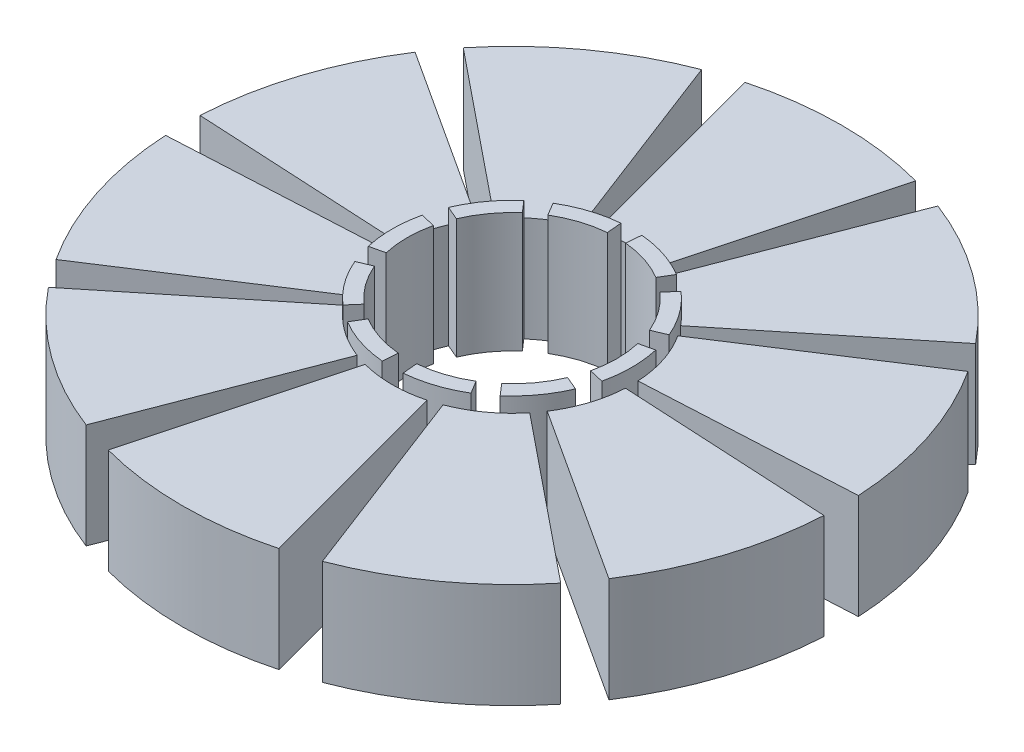
SolidWorks part; units mm, degrees
material "Copper"
ref_plane "Front Plane" through (0, 0, 0) normal (0, 0, 1) x (1, 0, 0)
ref_plane "Top Plane" through (0, 0, 0) normal (0, 1, 0) x (1, 0, 0)
ref_plane "Right Plane" through (0, 0, 0) normal (1, 0, 0) x (0, 0, -1)
sketch "Sketch2" plane through (0, 0, 0) normal (0, 1, 0) x (1, 0, 0)
  line L0 (0, 0) -> (0, 8) construction
  line L1 (0, 0) -> (1.8117, 6.7615) construction
  line L2 (0, 0) -> (-1.8117, 6.7615) construction
  line L3 (-5.694, 21.2504) -> (-2.0706, 7.7274)
  line L4 (2.0706, 7.7274) -> (5.694, 21.2504)
  line L5 (0, 0) -> (4.7023, 6.4721) construction
  line L6 (7.8841, 20.5388) -> (2.8669, 7.4686)
  line L7 (6.2172, 5.0346) -> (17.0972, 13.845)
  line L8 (0, 0) -> (7.6085, 2.4721) construction
  line L9 (18.4508, 11.9821) -> (6.7094, 4.3571)
  line L10 (7.989, 0.4187) -> (21.9698, 1.1514)
  line L11 (0, 0) -> (19.9722, -6.4894) construction
  line L12 (21.9698, -1.1514) -> (7.989, -0.4187)
  line L13 (6.7094, -4.3571) -> (18.4508, -11.9821)
  line L14 (0, 0) -> (4.7023, -6.4721) construction
  line L15 (17.0972, -13.845) -> (6.2172, -5.0346)
  line L16 (2.8669, -7.4686) -> (7.8841, -20.5388)
  line L17 (0, 0) -> (0, -8) construction
  line L18 (5.694, -21.2504) -> (2.0706, -7.7274)
  line L19 (-2.0706, -7.7274) -> (-5.694, -21.2504)
  line L20 (0, 0) -> (-4.7023, -6.4721) construction
  line L21 (-7.8841, -20.5388) -> (-2.8669, -7.4686)
  line L22 (-6.2172, -5.0346) -> (-17.0972, -13.845)
  line L23 (0, 0) -> (-7.6085, -2.4721) construction
  line L24 (-18.4508, -11.9821) -> (-6.7094, -4.3571)
  line L25 (-7.989, -0.4187) -> (-21.9698, -1.1514)
  line L26 (0, 0) -> (-7.6085, 2.4721) construction
  line L27 (-21.9698, 1.1514) -> (-7.989, 0.4187)
  line L28 (-6.7094, 4.3571) -> (-18.4508, 11.9821)
  line L29 (0, 0) -> (-4.7023, 6.4721) construction
  line L30 (-17.0972, 13.845) -> (-6.2172, 5.0346)
  line L31 (-2.8669, 7.4686) -> (-7.8841, 20.5388)
  line L32 (0.6101, 6.9734) -> (0.6972, 7.9696)
  line L33 (-0.6972, 7.9696) -> (-0.6101, 6.9734)
  line L34 (4.1203, 6.8573) -> (3.6053, 6.0002)
  line L35 (4.5924, 5.283) -> (5.2485, 6.0377)
  line L36 (7.364, 3.1258) -> (6.4435, 2.7351)
  line L37 (6.8206, 1.5747) -> (7.795, 1.7996)
  line L38 (7.795, -1.7996) -> (6.8206, -1.5747)
  line L39 (6.4435, -2.7351) -> (7.364, -3.1258)
  line L40 (5.2485, -6.0377) -> (4.5924, -5.283)
  line L41 (3.6053, -6.0002) -> (4.1203, -6.8573)
  line L42 (0.6972, -7.9696) -> (0.6101, -6.9734)
  line L43 (-0.6101, -6.9734) -> (-0.6972, -7.9696)
  line L44 (-4.1203, -6.8573) -> (-3.6053, -6.0002)
  line L45 (-4.5924, -5.283) -> (-5.2485, -6.0377)
  line L46 (-7.364, -3.1258) -> (-6.4435, -2.7351)
  line L47 (-6.8206, -1.5747) -> (-7.795, -1.7996)
  line L48 (-7.795, 1.7996) -> (-6.8206, 1.5747)
  line L49 (-6.4435, 2.7351) -> (-7.364, 3.1258)
  line L50 (-5.2485, 6.0377) -> (-4.5924, 5.283)
  line L51 (-3.6053, 6.0002) -> (-4.1203, 6.8573)
  line L52 (2.0706, 7.7274) -> (5.694, 21.2504) construction
  line L53 (-2.0706, 7.7274) -> (-5.694, 21.2504) construction
  arc A0 (5.694, 21.2504) -> (-5.694, 21.2504) centre (0, 0) ccw
  arc A1 (-6.4435, -2.7351) -> (-4.5924, -5.283) centre (0, 0) ccw
  arc A3 (-7.989, 0.4187) -> (-7.989, -0.4187) centre (0, 0) ccw
  arc A4 (-1.8117, 6.7615) -> (-0.6101, 6.9734) centre (0, 0) cw
  arc A5 (5.694, 21.2504) -> (-5.694, 21.2504) centre (0, 0) ccw
  arc A6 (17.0972, 13.845) -> (7.8841, 20.5388) centre (0, 0) ccw
  arc A7 (2.5086, 6.5351) -> (3.6053, 6.0002) centre (0, 0) cw
  arc A8 (21.9698, 1.1514) -> (18.4508, 11.9821) centre (0, 0) ccw
  arc A9 (5.8707, 3.8125) -> (6.4435, 2.7351) centre (0, 0) cw
  arc A10 (18.4508, -11.9821) -> (21.9698, -1.1514) centre (0, 0) ccw
  arc A11 (6.9904, -0.3664) -> (6.8206, -1.5747) centre (0, 0) cw
  arc A12 (7.8841, -20.5388) -> (17.0972, -13.845) centre (0, 0) ccw
  arc A13 (5.44, -4.4052) -> (4.5924, -5.283) centre (0, 0) cw
  arc A14 (-5.694, -21.2504) -> (5.694, -21.2504) centre (0, 0) ccw
  arc A15 (1.8117, -6.7615) -> (0.6101, -6.9734) centre (0, 0) cw
  arc A16 (-17.0972, -13.845) -> (-7.8841, -20.5388) centre (0, 0) ccw
  arc A17 (-2.5086, -6.5351) -> (-3.6053, -6.0002) centre (0, 0) cw
  arc A18 (-21.9698, -1.1514) -> (-18.4508, -11.9821) centre (0, 0) ccw
  arc A19 (-5.8707, -3.8125) -> (-6.4435, -2.7351) centre (0, 0) cw
  arc A20 (-18.4508, 11.9821) -> (-21.9698, 1.1514) centre (0, 0) ccw
  arc A21 (-6.9904, 0.3664) -> (-6.8206, 1.5747) centre (0, 0) cw
  arc A22 (-7.8841, 20.5388) -> (-17.0972, 13.845) centre (0, 0) ccw
  arc A23 (-5.44, 4.4052) -> (-2.5086, 6.5351) centre (0, 0) cw
  arc A24 (0.6972, 7.9696) -> (-0.6972, 7.9696) centre (0, 0) ccw
  circle A26 centre (0, 0) radius 7 construction
  arc A27 (-6.8206, -1.5747) -> (-6.9904, -0.3664) centre (0, 0) cw
  arc A28 (-6.8206, 1.5747) -> (-6.8206, -1.5747) centre (0, 0) ccw
  arc A29 (-6.4435, 2.7351) -> (-5.8707, 3.8125) centre (0, 0) cw
  circle A30 centre (0, 0) radius 8 construction
  arc A31 (-7.364, 3.1258) -> (-7.795, 1.7996) centre (0, 0) ccw
  arc A32 (-6.2172, 5.0346) -> (-6.7094, 4.3571) centre (0, 0) ccw
  arc A33 (-4.1203, 6.8573) -> (-5.2485, 6.0377) centre (0, 0) ccw
  arc A34 (-2.0706, 7.7274) -> (-2.8669, 7.4686) centre (0, 0) ccw
  arc A35 (0.6972, 7.9696) -> (-0.6972, 7.9696) centre (0, 0) ccw
  arc A36 (-0.6101, 6.9734) -> (-6.4435, 2.7351) centre (0, 0) ccw
  arc A37 (0.6101, 6.9734) -> (1.8117, 6.7615) centre (0, 0) cw
  arc A38 (2.8669, 7.4686) -> (2.0706, 7.7274) centre (0, 0) ccw
  arc A39 (3.6053, 6.0002) -> (0.6101, 6.9734) centre (0, 0) ccw
  arc A40 (4.5924, 5.283) -> (5.44, 4.4052) centre (0, 0) cw
  arc A41 (5.2485, 6.0377) -> (4.1203, 6.8573) centre (0, 0) ccw
  arc A42 (6.7094, 4.3571) -> (6.2172, 5.0346) centre (0, 0) ccw
  arc A43 (6.4435, 2.7351) -> (4.5924, 5.283) centre (0, 0) ccw
  arc A44 (6.8206, 1.5747) -> (6.9904, 0.3664) centre (0, 0) cw
  arc A45 (7.795, 1.7996) -> (7.364, 3.1258) centre (0, 0) ccw
  arc A46 (-5.2485, -6.0377) -> (-4.1203, -6.8573) centre (0, 0) ccw
  arc A47 (-3.6053, -6.0002) -> (-0.6101, -6.9734) centre (0, 0) ccw
  arc A48 (-4.5924, -5.283) -> (-5.44, -4.4052) centre (0, 0) cw
  arc A49 (-2.8669, -7.4686) -> (-2.0706, -7.7274) centre (0, 0) ccw
  arc A50 (-0.6972, -7.9696) -> (0.6972, -7.9696) centre (0, 0) ccw
  arc A51 (2.0706, -7.7274) -> (2.8669, -7.4686) centre (0, 0) ccw
  arc A52 (-0.6101, -6.9734) -> (-1.8117, -6.7615) centre (0, 0) cw
  arc A53 (0.6101, -6.9734) -> (3.6053, -6.0002) centre (0, 0) ccw
  arc A54 (3.6053, -6.0002) -> (2.5086, -6.5351) centre (0, 0) cw
  arc A55 (4.5924, -5.283) -> (6.4435, -2.7351) centre (0, 0) ccw
  arc A56 (6.8206, -1.5747) -> (6.8206, 1.5747) centre (0, 0) ccw
  arc A57 (6.4435, -2.7351) -> (5.8707, -3.8125) centre (0, 0) cw
  arc A58 (4.1203, -6.8573) -> (5.2485, -6.0377) centre (0, 0) ccw
  arc A59 (6.2172, -5.0346) -> (6.7094, -4.3571) centre (0, 0) ccw
  arc A60 (7.364, -3.1258) -> (7.795, -1.7996) centre (0, 0) ccw
  arc A61 (7.989, -0.4187) -> (7.989, 0.4187) centre (0, 0) ccw
  arc A62 (-6.7094, -4.3571) -> (-6.2172, -5.0346) centre (0, 0) ccw
  arc A63 (-7.795, -1.7996) -> (-7.364, -3.1258) centre (0, 0) ccw
  arc A66 (17.0972, 13.845) -> (7.8841, 20.5388) centre (0, 0) ccw
  arc A68 (21.9698, 1.1514) -> (18.4508, 11.9821) centre (0, 0) ccw
  arc A70 (18.4508, -11.9821) -> (21.9698, -1.1514) centre (0, 0) ccw
  arc A73 (7.8841, -20.5388) -> (17.0972, -13.845) centre (0, 0) ccw
  arc A75 (-5.694, -21.2504) -> (5.694, -21.2504) centre (0, 0) ccw
  arc A77 (-17.0972, -13.845) -> (-7.8841, -20.5388) centre (0, 0) ccw
  arc A78 (-21.9698, -1.1514) -> (-18.4508, -11.9821) centre (0, 0) ccw
  arc A80 (-18.4508, 11.9821) -> (-21.9698, 1.1514) centre (0, 0) ccw
  arc A82 (-7.8841, 20.5388) -> (-17.0972, 13.845) centre (0, 0) ccw
  point P62 (0, 0)
  point P106 (0, 0)
  dimension "D1" = 44
  dimension "D2" = 14
  dimension "D5" = 15
  dimension "D6" = 15
  dimension "D8" = 10
  dimension "D9" = 5
  dimension "D4" = 1
  dimension "D7" = 10
  dimension "D10" = 10
extrude "Boss-Extrude1" add sketch "Sketch2" along normal blind 7 contours L24 A62 L22 A16 L21 A49 L19 A14 L18 A51 L16 A12 L15 A59 L13 A10 L12 A61 L10 A8 L9 A42 L7 A6 L6 A38 L4 A0 L3 A34 L31 A22 L30 A32 L28 A20 L27 A3 L25 A18 A63 L47 A27 A28 A21 L48 A31 L49 A29 A36 region at (0, 0, -21.3782)
sketch "Sketch3" plane through (0, 7, 0) normal (0, 1, 0) x (1, 0, 0)
  line L0 (-7.795, 1.7996) -> (-6.8206, 1.5747) construction
  line L1 (-6.8206, -1.5747) -> (-7.795, -1.7996) construction
  line L2 (-7.364, -3.1258) -> (-6.4435, -2.7351) construction
  line L3 (-4.5924, -5.283) -> (-5.2485, -6.0377) construction
  line L4 (-4.1203, -6.8573) -> (-3.6053, -6.0002) construction
  line L5 (-0.6101, -6.9734) -> (-0.6972, -7.9696) construction
  line L6 (0.6972, -7.9696) -> (0.6101, -6.9734) construction
  line L7 (3.6053, -6.0002) -> (4.1203, -6.8573) construction
  line L8 (5.2485, -6.0377) -> (4.5924, -5.283) construction
  line L9 (6.4435, -2.7351) -> (7.364, -3.1258) construction
  line L10 (7.795, -1.7996) -> (6.8206, -1.5747) construction
  line L11 (6.8206, 1.5747) -> (7.795, 1.7996) construction
  line L12 (7.364, 3.1258) -> (6.4435, 2.7351) construction
  line L13 (4.1203, 6.8573) -> (3.6053, 6.0002) construction
  line L14 (0.6101, 6.9734) -> (0.6972, 7.9696) construction
  line L15 (-0.6972, 7.9696) -> (-0.6101, 6.9734) construction
  line L16 (-3.6053, 6.0002) -> (-4.1203, 6.8573) construction
  line L17 (-5.2485, 6.0377) -> (-4.5924, 5.283) construction
  line L18 (-6.4435, 2.7351) -> (-7.364, 3.1258) construction
  line L19 (-7.795, 1.7996) -> (-6.8206, 1.5747)
  line L20 (-6.8206, -1.5747) -> (-7.795, -1.7996)
  line L21 (-7.364, -3.1258) -> (-6.4435, -2.7351)
  line L22 (-4.5924, -5.283) -> (-5.2485, -6.0377)
  line L23 (-4.1203, -6.8573) -> (-3.6053, -6.0002)
  line L24 (-0.6101, -6.9734) -> (-0.6972, -7.9696)
  line L25 (0.6972, -7.9696) -> (0.6101, -6.9734)
  line L26 (3.6053, -6.0002) -> (4.1203, -6.8573)
  line L27 (5.2485, -6.0377) -> (4.5924, -5.283)
  line L28 (6.4435, -2.7351) -> (7.364, -3.1258)
  line L29 (7.795, -1.7996) -> (6.8206, -1.5747)
  line L30 (6.8206, 1.5747) -> (7.795, 1.7996)
  line L31 (7.364, 3.1258) -> (6.4435, 2.7351)
  line L32 (4.1203, 6.8573) -> (3.6053, 6.0002)
  line L33 (0.6101, 6.9734) -> (0.6972, 7.9696)
  line L34 (-0.6972, 7.9696) -> (-0.6101, 6.9734)
  line L35 (-3.6053, 6.0002) -> (-4.1203, 6.8573)
  line L36 (-5.2485, 6.0377) -> (-4.5924, 5.283)
  line L37 (-6.4435, 2.7351) -> (-7.364, 3.1258)
  line L38 (4.5924, 5.283) -> (5.2485, 6.0377) construction
  line L39 (4.5924, 5.283) -> (5.2485, 6.0377)
  arc A0 (-7.795, 1.7996) -> (-7.795, -1.7996) centre (0, 0) ccw
  arc A1 (-6.8206, 1.5747) -> (-6.8206, -1.5747) centre (0, 0) ccw construction
  arc A2 (-6.4435, -2.7351) -> (-4.5924, -5.283) centre (0, 0) ccw construction
  arc A3 (-3.6053, -6.0002) -> (-0.6101, -6.9734) centre (0, 0) ccw construction
  arc A4 (0.6101, -6.9734) -> (3.6053, -6.0002) centre (0, 0) ccw construction
  arc A5 (4.5924, -5.283) -> (6.4435, -2.7351) centre (0, 0) ccw construction
  arc A6 (6.8206, -1.5747) -> (6.8206, 1.5747) centre (0, 0) ccw construction
  arc A7 (6.4435, 2.7351) -> (4.5924, 5.283) centre (0, 0) ccw construction
  arc A8 (3.6053, 6.0002) -> (0.6101, 6.9734) centre (0, 0) ccw construction
  arc A9 (-0.6101, 6.9734) -> (-3.6053, 6.0002) centre (0, 0) ccw construction
  arc A10 (-4.5924, 5.283) -> (-6.4435, 2.7351) centre (0, 0) ccw construction
  arc A11 (-6.8206, 1.5747) -> (-6.8206, -1.5747) centre (0, 0) ccw
  arc A12 (-6.4435, -2.7351) -> (-4.5924, -5.283) centre (0, 0) ccw
  arc A13 (-3.6053, -6.0002) -> (-0.6101, -6.9734) centre (0, 0) ccw
  arc A14 (0.6101, -6.9734) -> (3.6053, -6.0002) centre (0, 0) ccw
  arc A15 (4.5924, -5.283) -> (6.4435, -2.7351) centre (0, 0) ccw
  arc A16 (6.8206, -1.5747) -> (6.8206, 1.5747) centre (0, 0) ccw
  arc A17 (6.4435, 2.7351) -> (4.5924, 5.283) centre (0, 0) ccw
  arc A18 (3.6053, 6.0002) -> (0.6101, 6.9734) centre (0, 0) ccw
  arc A19 (-0.6101, 6.9734) -> (-3.6053, 6.0002) centre (0, 0) ccw
  arc A20 (-4.5924, 5.283) -> (-6.4435, 2.7351) centre (0, 0) ccw
  arc A21 (-5.2485, 6.0377) -> (-7.364, 3.1258) centre (0, 0) ccw
  arc A22 (-7.364, -3.1258) -> (-5.2485, -6.0377) centre (0, 0) ccw
  arc A23 (-4.1203, -6.8573) -> (-0.6972, -7.9696) centre (0, 0) ccw
  arc A24 (5.2485, -6.0377) -> (7.364, -3.1258) centre (0, 0) ccw
  arc A25 (7.364, 3.1258) -> (5.2485, 6.0377) centre (0, 0) ccw
  arc A26 (-0.6972, 7.9696) -> (-4.1203, 6.8573) centre (0, 0) ccw
  arc A27 (4.1203, 6.8573) -> (0.6972, 7.9696) centre (0, 0) ccw
  arc A28 (7.795, -1.7996) -> (7.795, 1.7996) centre (0, 0) ccw
  arc A29 (0.6972, -7.9696) -> (4.1203, -6.8573) centre (0, 0) ccw
extrude "Boss-Extrude2" add sketch "Sketch3" along normal blind 1
